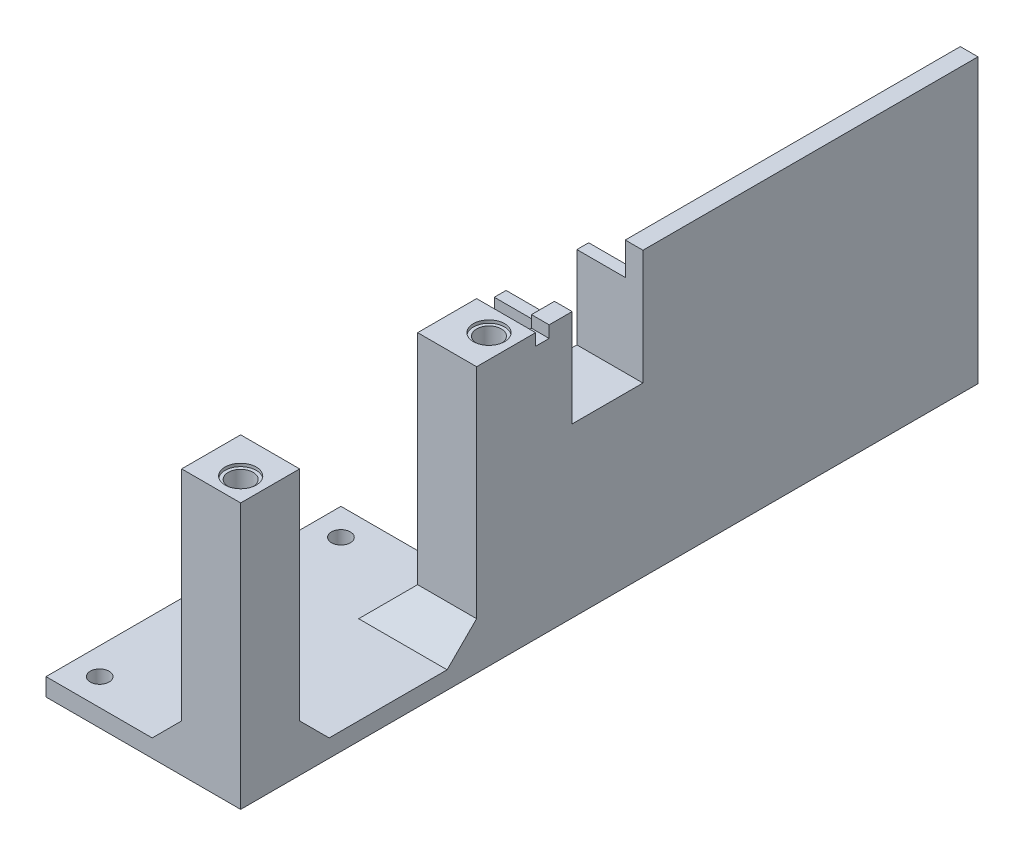
SolidWorks part; units mm, degrees
ref_plane "Front Plane" through (0, 0, 0) normal (0, 0, 1) x (1, 0, 0)
ref_plane "Top Plane" through (0, 0, 0) normal (0, 1, 0) x (1, 0, 0)
ref_plane "Right Plane" through (0, 0, 0) normal (1, 0, 0) x (0, 0, -1)
sketch "Sketch1" plane through (0, 0, 0) normal (0, 1, 0) x (1, 0, 0)
  line L1 (-6.5124, 9.686) -> (1.4876, 9.686)
  line L2 (-6.5124, 9.686) -> (-6.5124, -40.314)
  line L3 (-6.5124, -40.314) -> (1.4876, -40.314)
  line L4 (1.4876, 9.686) -> (1.4876, -40.314)
  line L5 (1.4876, 9.686) -> (26.4876, 9.686)
  line L6 (1.4876, 9.686) -> (1.4876, -40.314)
  line L7 (1.4876, -40.314) -> (26.4876, -40.314)
  line L8 (26.4876, 9.686) -> (26.4876, -40.314)
  circle A0 centre (-1.9624, -35.764) radius 1.6
  circle A1 centre (-1.9624, 5.136) radius 1.6
  dimension "D4" = 3.2
  dimension "D5" = 3.2
  dimension "D6" = 4.55
  dimension "D7" = 4.55
  dimension "D8" = 4.55
  dimension "D9" = 4.55
  dimension "D1" = 8
  dimension "D2" = 50
  dimension "D3" = 25
extrude "Boss-Extrude1" add sketch "Sketch1" along normal blind 3 contours A1 | A0 | L5 L8 L7 L3 L2 L1
sketch "Sketch2" plane through (0, 3, 0) normal (0, 1, 0) x (1, 0, 0)
  line L1 (26.4876, -40.314) -> (16.4876, -40.314)
  line L2 (26.4876, -40.314) -> (26.4876, -30.314)
  line L3 (26.4876, -30.314) -> (16.4876, -30.314)
  line L4 (16.4876, -40.314) -> (16.4876, -30.314)
  line L5 (26.4876, 9.686) -> (16.4876, 9.686)
  line L6 (26.4876, 9.686) -> (26.4876, -0.314)
  line L7 (26.4876, -0.314) -> (16.4876, -0.314)
  line L8 (16.4876, 9.686) -> (16.4876, -0.314)
  dimension "D1" = 10
  dimension "D2" = 10
  dimension "D3" = 10
  dimension "D4" = 10
extrude "Boss-Extrude2" add sketch "Sketch2" along normal blind 42
chamfer "Chamfer1" distance 5 angle 45 4 edges at (16.4876, 3, -4.686) (21.4876, 3, 0.314) (16.4876, 3, 35.314) (21.4876, 3, 30.314)
ref_plane "Plane1" through (0, 45, 0) normal (0, 1, 0) x (1, 0, 0)
sketch "Sketch3" plane through (0, 45, 0) normal (0, 1, 0) x (1, 0, 0)
  line L0 (26.4876, -40.314) -> (26.4876, -30.314) construction
  line L1 (16.4876, -40.314) -> (26.4876, -40.314) construction
  line L2 (26.4876, -0.314) -> (26.4876, 9.686) construction
  line L3 (26.4876, 9.686) -> (16.4876, 9.686) construction
  circle A0 centre (22.5376, -36.364) radius 2.1
  circle A1 centre (22.5376, 5.736) radius 2.1
  dimension "D1" = 4.2
  dimension "D3" = 3.95
  dimension "D4" = 4.2
  dimension "D6" = 3.95
  dimension "D2" = 3.95
  dimension "D5" = 3.95
extrude "Cut-Extrude1" cut sketch "Sketch3" against normal blind 52
sketch "Sketch4" plane through (0, 45, 0) normal (0, 1, 0) x (1, 0, 0)
  circle A0 centre (22.5376, -36.364) radius 2.65
  circle A1 centre (22.5376, 5.736) radius 2.65
  dimension "D1" = 5.3
  dimension "D2" = 5.3
extrude "Cut-Extrude2" cut sketch "Sketch4" against normal blind 0.5
ref_plane "Plane2" through (0, 22.5, 0) normal (0, -1, 0) x (-1, 0, 0)
mirror "Mirror1" about plane through (0, 22.5, 0) normal (0, -1, 0) of "Cut-Extrude2"
sketch "Sketch5" plane through (0, 0, -9.686) normal (0, 0, -1) x (-1, 0, 0)
  line L0 (-26.4876, 45) -> (-26.4876, 0) construction
  line L1 (-26.4876, 43) -> (-23.4876, 43)
  line L2 (-26.4876, 43) -> (-26.4876, 0)
  line L3 (-26.4876, 0) -> (-23.4876, 0)
  line L4 (-23.4876, 43) -> (-23.4876, 0)
  line L5 (6.5124, 0) -> (-26.4876, 0) construction
  line L6 (5.5, 45) -> (-5.5, 45) construction
  dimension "D1" = 3
  dimension "D2" = 2
extrude "Boss-Extrude3" add sketch "Sketch5" along normal blind 75
sketch "Sketch6" plane through (0, 43, 0) normal (0, 1, 0) x (1, 0, 0)
  line L0 (23.4876, 84.686) -> (23.4876, 9.686) construction
  line L1 (23.4876, 11.986) -> (26.4876, 11.986)
  line L2 (23.4876, 11.986) -> (23.4876, 84.686)
  line L3 (23.4876, 84.686) -> (26.4876, 84.686)
  line L4 (26.4876, 11.986) -> (26.4876, 84.686)
  line L5 (26.4876, 9.686) -> (16.4876, 9.686) construction
  dimension "D1" = 2.3
extrude "Boss-Extrude4" add sketch "Sketch6" along normal blind 2
sketch "Sketch7" plane through (0, 45, 0) normal (0, 1, 0) x (1, 0, 0)
  line L0 (26.4876, 11.986) -> (26.4876, 84.686) construction
  line L1 (23.4876, 84.686) -> (26.4876, 84.686)
  line L2 (23.4876, 84.686) -> (23.4876, 15.886)
  line L3 (23.4876, 15.886) -> (26.4876, 15.886)
  line L4 (26.4876, 84.686) -> (26.4876, 15.886)
  line L5 (23.4876, 11.986) -> (26.4876, 11.986) construction
  dimension "D1" = 3.9
extrude "Boss-Extrude5" add sketch "Sketch7" along normal blind 3
sketch "Sketch8" plane through (23.4876, 0, 0) normal (-1, 0, 0) x (0, 0, 1)
  line L0 (-84.686, 48) -> (-15.886, 48) construction
  line L1 (-15.886, 28.5) -> (-27.886, 28.5)
  line L2 (-15.886, 28.5) -> (-15.886, 22.5)
  line L3 (-15.886, 22.5) -> (-27.886, 22.5)
  line L4 (-27.886, 28.5) -> (-27.886, 22.5)
  line L5 (-15.886, 48) -> (-15.886, 45) construction
  line L6 (-15.886, 24.5) -> (-27.886, 24.5) construction
  line L7 (-15.886, 28.5) -> (-15.886, 42.5)
  line L8 (-27.886, 22.5) -> (-29.886, 22.5)
  line L9 (-27.886, 22.5) -> (-27.886, 42.5)
  line L10 (-27.886, 42.5) -> (-29.886, 42.5)
  line L11 (-29.886, 22.5) -> (-29.886, 42.5)
  line L12 (-15.886, 22.5) -> (-13.886, 22.5)
  line L13 (-15.886, 22.5) -> (-15.886, 42.5)
  line L14 (-15.886, 42.5) -> (-13.886, 42.5)
  line L15 (-13.886, 22.5) -> (-13.886, 42.5)
  circle A0 centre (-21.886, 24.5) radius 1
  dimension "D5" = 2
  dimension "D1" = 19.5
  dimension "D2" = 6
  dimension "D3" = 12
  dimension "D4" = 2
  dimension "D6" = 2
  dimension "D7" = 2
  dimension "D8" = 20
extrude "Boss-Extrude7" add sketch "Sketch8" along normal blind 8.2 contours L11 L8 L9 L4 L10 | L6 L2 L1 L4 A0 | L13 L6 A0 L9 L3 | L12 L15 L14 L7 L2 L13 region at (23.4876, 26.5533, -21.886) region at (23.4876, 32.5, -14.886) region at (23.4876, 32.5, -28.886) region at (23.4876, 23.4597, -21.886)
sketch "Sketch9" plane through (23.4876, 0, 0) normal (-1, 0, 0) x (0, 0, 1)
  line L0 (-84.686, 48) -> (-15.886, 48) construction
  line L1 (-15.886, 28.5) -> (-27.886, 28.5)
  line L2 (-15.886, 28.5) -> (-15.886, 48)
  line L3 (-15.886, 48) -> (-27.886, 48)
  line L4 (-27.886, 28.5) -> (-27.886, 48)
extrude "Cut-Extrude3" cut sketch "Sketch9" against normal blind 8.5
